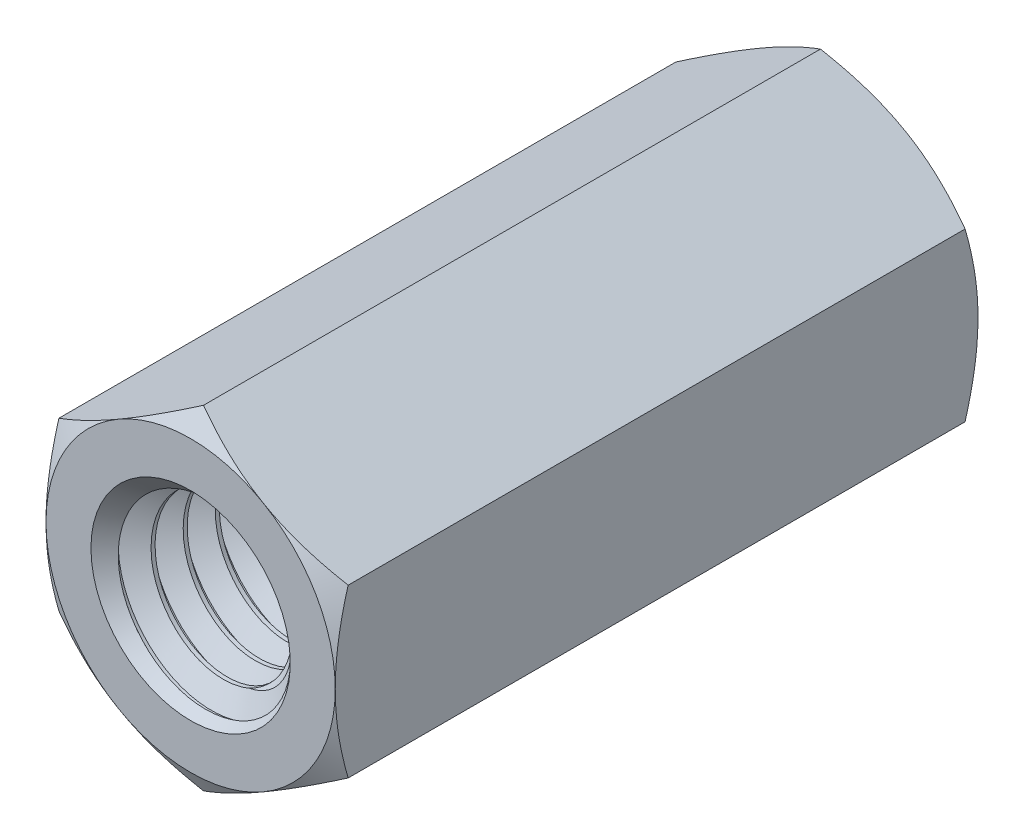
SolidWorks part; units mm, degrees
ref_plane "Front Plane" through (0, 0, 0) normal (0, 0, 1) x (1, 0, 0)
ref_plane "Top Plane" through (0, 0, 0) normal (0, 1, 0) x (1, 0, 0)
ref_plane "Right Plane" through (0, 0, 0) normal (1, 0, 0) x (0, 0, -1)
sketch "Sketch3" plane through (0, 0, 0) normal (1, 0, 0) x (0, 0, -1)
  line L0 (-5, 0) -> (5, 0) construction
  line L1 (0, 2.25) -> (0, -2.25) construction
  line L2 (-5, 1.5) -> (-5, -1.5) construction
  point P2 (0.2, 0)
  point P3 (-0.2, 0)
  dimension "D1" = 4.8
  dimension "Length" = 10
  dimension "Min Thread Length" = 4.8
  dimension "Thread Dia" = 3
  dimension "Hex" = 4.5
sketch "Sketch1" plane through (0, 0, 0) normal (0, 0, 1) x (1, 0, 0)
  line L1 (0, 2.5981) -> (-2.25, 1.299)
  line L2 (-2.25, 1.299) -> (-2.25, -1.299)
  line L3 (-2.25, -1.299) -> (0, -2.5981)
  line L4 (0, -2.5981) -> (2.25, -1.299)
  line L5 (2.25, -1.299) -> (2.25, 1.299)
  line L6 (2.25, 1.299) -> (0, 2.5981)
  circle A0 centre (0, 0) radius 2.25 construction
  circle A1 centre (0, 0) radius 1.5
extrude "Extrude1" add sketch "Sketch1" along normal up to vertex (5 mm away) and the other way up to vertex (5 mm away) up to point (0, 0, 5) other way up to point (0, 0, -5)
sketch "Sketch11" plane through (0, 0, -5) normal (0, 0, -1) x (-1, 0, 0)
  circle A0 centre (0, 0) radius 1.5 construction
  circle A1 centre (0, 0) radius 1.5
curve "Helix/Spiral1" pitch 0.5 height 10.5 radius 1.5 centre (0, 0, -5) axis (0, 0, 1) start towards (0, 1, 0) parameters "Pitch"=0.5
sketch "Sketch12" plane through (0, 0, 0) normal (1, 0, 0) x (0, 0, -1)
  line L0 (5.4375, 1.5) -> (5, 1.5)
  line L1 (5.4375, 1.5) -> (5.25, 1.1752)
  line L2 (5.25, 1.1752) -> (5.1875, 1.1752)
  line L3 (5.1875, 1.1752) -> (5, 1.5)
  line L4 (5.2187, 1.1752) -> (5.2187, 1.5) construction
  line L5 (5.3438, 1.3376) -> (5.0938, 1.3376) construction
  dimension "D1" = 0.0625
  dimension "D2" = 0.25
  dimension "D3" = 60
sweep "Sweep1" add profiles "Sketch12" path "Helix/Spiral1"
sketch "Sketch6" plane through (0, 0, -5) normal (0, 0, -1) x (-1, 0, 0)
  line L6 (0, 2.5981) -> (-2.25, 1.299)
  line L7 (-2.25, 1.299) -> (-2.25, -1.299)
  line L8 (-2.25, -1.299) -> (0, -2.5981)
  line L9 (0, -2.5981) -> (2.25, -1.299)
  line L10 (2.25, -1.299) -> (2.25, 1.299)
  line L11 (2.25, 1.299) -> (0, 2.5981)
  line L12 (0, 2.5981) -> (-2.25, 1.299)
  line L13 (-2.25, 1.299) -> (-2.25, -1.299)
  line L14 (-2.25, -1.299) -> (0, -2.5981)
  line L15 (0, -2.5981) -> (2.25, -1.299)
  line L16 (2.25, -1.299) -> (2.25, 1.299)
  line L17 (2.25, 1.299) -> (0, 2.5981)
  dimension "D1" = 0
extrude "Extrude2" cut sketch "Sketch6" along normal through all
sketch "Sketch7" plane through (0, 0, -5) normal (0, 0, -1) x (-1, 0, 0)
  circle A2 centre (0, 0) radius 1.5508
  circle A3 centre (0, 0) radius 1.5508
  dimension "D1" = 0.0508
extrude "Extrude3" cut sketch "Sketch7" against normal through all draft 43
sketch "Sketch8" plane through (0, 0, -5) normal (0, 0, -1) x (-1, 0, 0)
  circle A0 centre (0, 0) radius 2.25 construction
  circle A1 centre (0, 0) radius 2.25
extrude "Extrude4" cut sketch "Sketch8" against normal through all draft 60 flip side to cut
mirror "Mirror1" about plane through (0, 0, 0) normal (0, 0, 1) of "Extrude2", "Extrude3", "Extrude4"
sketch "Sketch9" [suppressed] plane through (0, 0, 0) normal (1, 0, 0) x (0, 0, -1)
  line L1 (-1.2, 1.1353) -> (1.2, 1.1353)
  line L2 (-1.2, 1.1353) -> (-1.2, 0)
  line L3 (-1.2, 0) -> (1.2, 0)
  line L4 (1.2, 1.1353) -> (1.2, 0)
  line L7 (-6, 0) -> (6, 0) construction
revolve "Revolve" [suppressed] add sketch "Sketch9" angle 360 about L0
sketch "Sketch10" [suppressed] plane through (0, 0, 0) normal (1, 0, 0) x (0, 0, -1)
  line L0 (6, 1.25) -> (1.2, 1.25)
  line L1 (-6, 1.25) -> (-1.2, 1.25)
  line L2 (1.2, 1.25) -> (1.2, -1.25)
  line L3 (-6, -1.25) -> (-1.2, -1.25)
  line L4 (-1.2, 1.25) -> (-1.2, -1.25)
  line L5 (1.2, -1.25) -> (6, -1.25)
equation "\"D1@Sketch3\" = \"Min Thread Length@Sketch3\""
equation "\"D3@Helix/Spiral1\" = \"Length@Sketch3\"+\"Pitch@Helix/Spiral1\""
equation "\"D1@Sketch12\" = \"Pitch@Helix/Spiral1\"*.125"
equation "\"D2@Sketch12\" = \"Pitch@Helix/Spiral1\"*.5"
